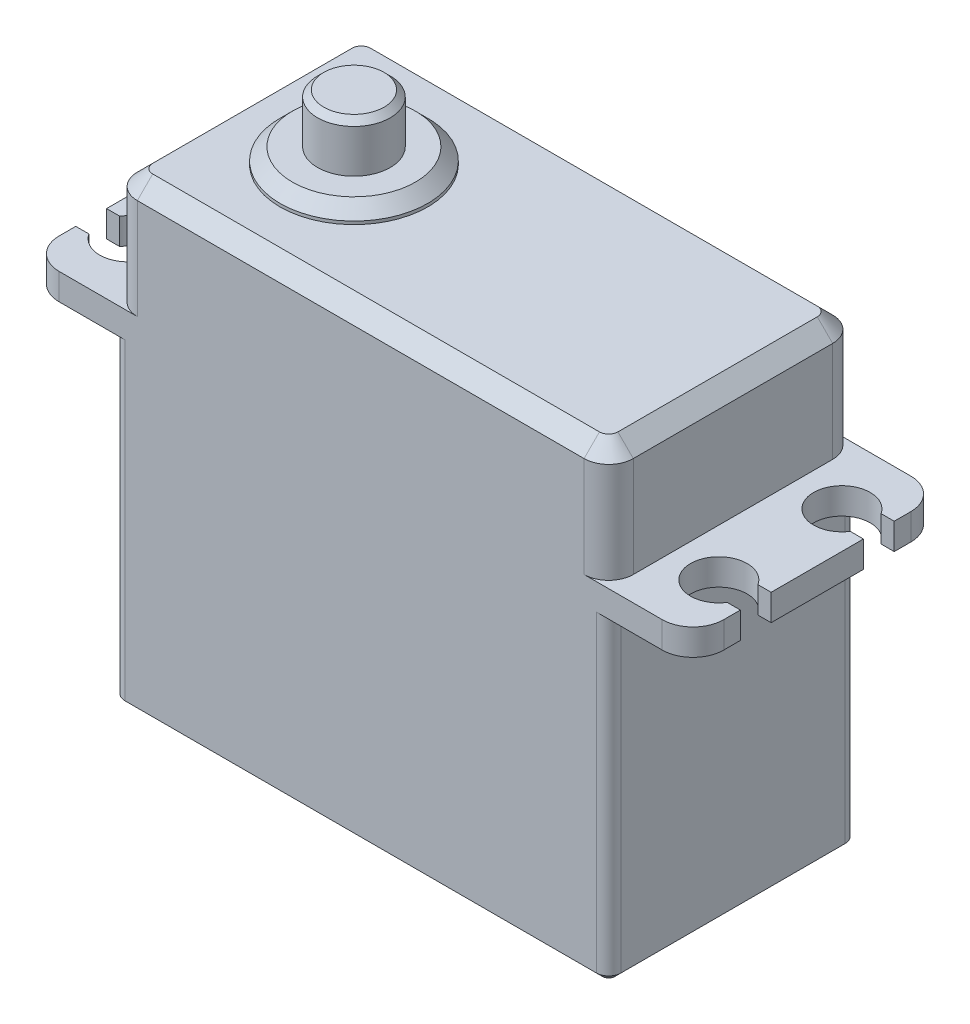
SolidWorks part; units mm, degrees
material "6061-T6 (SS)"
ref_plane "Front Plane" through (0, 0, 0) normal (0, 0, 1) x (1, 0, 0)
ref_plane "Top Plane" through (0, 0, 0) normal (0, 1, 0) x (1, 0, 0)
ref_plane "Right Plane" through (0, 0, 0) normal (1, 0, 0) x (0, 0, -1)
sketch "Sketch2" plane through (0, 0, 0) normal (0, 1, 0) x (1, 0, 0)
  line L1 (-20.15, 10.1) -> (20.15, 10.1)
  line L2 (-20.15, 10.1) -> (-20.15, -10.1)
  line L3 (-20.15, -10.1) -> (20.15, -10.1)
  line L4 (20.15, 10.1) -> (20.15, -10.1)
  line L5 (-20.15, 10.1) -> (20.15, -10.1) construction
  line L6 (-20.15, -10.1) -> (20.15, 10.1) construction
  point P0 (0, 0)
  dimension "D1" = 20.2
  dimension "D2" = 40.3
extrude "Boss-Extrude1" add sketch "Sketch2" along normal mid plane 25.9
fillet "Fillet1" radius 1 4 edges at (-20.15, 0, -10.1) (20.15, 0, -10.1) (20.15, 0, 10.1) (-20.15, 0, 10.1)
sketch "Sketch3" plane through (0, 12.95, 0) normal (0, 1, 0) x (1, 0, 0)
  line L0 (19.15, 10.1) -> (-19.15, 10.1) construction
  line L1 (-27, 10.1) -> (27, 10.1)
  line L2 (-27, 10.1) -> (-27, -10.1)
  line L3 (-27, -10.1) -> (27, -10.1)
  line L4 (27, 10.1) -> (27, -10.1)
  line L5 (-27, 10.1) -> (27, -10.1) construction
  line L6 (-27, -10.1) -> (27, 10.1) construction
  point P0 (0, 0)
  dimension "D1" = 54
extrude "Boss-Extrude2" add sketch "Sketch3" along normal blind 2.14
fillet "Fillet2" radius 2.5 4 edges at (-27, 14.02, -10.1) (27, 14.02, -10.1) (27, 14.02, 10.1) (-27, 14.02, 10.1)
sketch "Sketch4" plane through (0, 15.09, 0) normal (0, 1, 0) x (1, 0, 0)
  line L0 (-24.5, -10.1) -> (24.5, -10.1) construction
  line L1 (-20.15, 10.1) -> (20.15, 10.1)
  line L2 (-20.15, 10.1) -> (-20.15, -10.1)
  line L3 (-20.15, -10.1) -> (20.15, -10.1)
  line L4 (20.15, 10.1) -> (20.15, -10.1)
  line L5 (-20.15, 10.1) -> (20.15, -10.1) construction
  line L6 (-20.15, -10.1) -> (20.15, 10.1) construction
  point P0 (0, 0)
  dimension "D1" = 40.3
extrude "Boss-Extrude3" add sketch "Sketch4" along normal blind 9.41
fillet "Fillet3" radius 2 4 edges at (20.15, 19.795, -10.1) (20.15, 19.795, 10.1) (-20.15, 19.795, -10.1) (-20.15, 19.795, 10.1)
fillet "Chamfer1" radius 1.25 8 edges at (-19.5642, 24.5, 9.5142) (-19.5642, 24.5, -9.5142) (19.5642, 24.5, -9.5142) (19.5642, 24.5, 9.5142) (20.15, 24.5, 0) (-20.15, 24.5, 0) (0, 24.5, -10.1) (0, 24.5, 10.1) profile chamfer
sketch "Sketch5" plane through (0, 24.5, 0) normal (0, 1, 0) x (1, 0, 0)
  line L0 (-20.5975, 0) -> (20.5975, 0) construction
  line L2 (-20.15, 8.1) -> (-20.15, -8.1) construction
  circle A0 centre (-10.65, 0) radius 6
  dimension "D1" = 12
  dimension "D2" = 9.5
extrude "Boss-Extrude4" add sketch "Sketch5" along normal blind 1.25
chamfer "Chamfer2" distance 1 angle 45 1 edges at (-10.65, 25.75, 6)
sketch "Sketch6" plane through (0, 25.75, 0) normal (0, 1, 0) x (1, 0, 0)
  circle A0 centre (-10.65, 0) radius 2.95
  dimension "D1" = 5.9
extrude "Boss-Extrude5" add sketch "Sketch6" along normal blind 4
chamfer "Chamfer3" distance 0.5 angle 45 1 edges at (-10.65, 29.75, 2.95)
sketch "Sketch7" plane through (0, 15.09, 0) normal (0, 1, 0) x (1, 0, 0)
  line L0 (-27, 7.6) -> (-27, -7.6) construction
  line L1 (-27, 6.25) -> (-25.9307, 6.25)
  line L2 (-27, 6.25) -> (-27, 3.75)
  line L7 (0, -11.11) -> (0, 11.11) construction
  line L8 (-27, 3.75) -> (-25.9307, 3.75)
  line L9 (-25.7, 6.25) -> (-25.7, 3.75) construction
  line L10 (-27, 6.25) -> (-25.7, 3.75) construction
  line L11 (-27, 3.75) -> (-25.7, 6.25) construction
  line L12 (-23.485, 0) -> (23.485, 0) construction
  line L13 (-25.9307, 6.25) -> (-25.7, 6.25) construction
  line L14 (-25.9307, 3.75) -> (-25.7, 3.75) construction
  arc A4 (-25.9307, 3.75) -> (-25.9307, 6.25) centre (-24, 5) ccw
  arc A5 (-26.2978, 4.8996) -> (-25.9307, 3.75) centre (-24, 5) ccw construction
  arc A6 (-26.2978, 5.1004) -> (-26.2978, 4.8996) centre (-24, 5) ccw construction
  arc A7 (-25.9307, 6.25) -> (-26.2978, 5.1004) centre (-24, 5) ccw construction
  point P2 (-26.35, 5)
  dimension "D1" = 4.6
  dimension "D2" = 24
  dimension "D3" = 2.5
  dimension "D4" = 1.3
  dimension "D5" = 5
extrude "Cut-Extrude1" cut sketch "Sketch7" against normal through all both and the other way through all
pattern_linear "LPattern1" count 2 spacing 10 along (0, 0, 1) of "Cut-Extrude1"
mirror "Mirror1" about plane through (0, 0, 0) normal (1, 0, 0) of "LPattern1"
chamfer "Chamfer4" distance 0.5 angle 45 8 edges at (0, -12.95, -10.1) (-19.8571, -12.95, -9.8071) (19.8571, -12.95, -9.8071) (-20.15, -12.95, 0) (20.15, -12.95, 0) (-19.8571, -12.95, 9.8071) (19.8571, -12.95, 9.8071) (0, -12.95, 10.1)
equation "\"servoWidth\"=20.2"
equation "\"servoLength\"=40.3"
equation "\"D2@Sketch2\"=\"servoLength\""
equation "\"D1@Sketch2\"=\"servoWidth\""
equation "\"servoHeight\"=37.45"
equation "\"servoHeight1\"=25.9"
equation "\"D1@Boss-Extrude1\"=\"servoHeight1\""
equation "\"D1@Sketch4\"=\"servoLength\""
equation "\"holeD\"=4.6"
equation "\"D1@Sketch7\"=\"holeD\""
